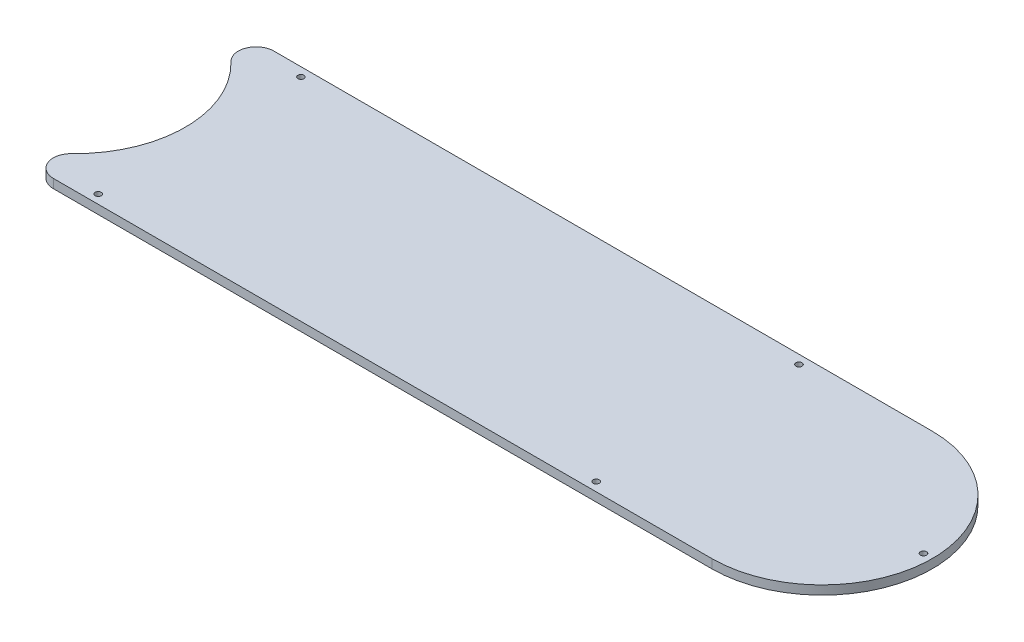
SolidWorks part; units mm, degrees
ref_plane "Front Plane" through (0, 0, 0) normal (0, 0, 1) x (1, 0, 0)
ref_plane "Top Plane" through (0, 0, 0) normal (0, 1, 0) x (1, 0, 0)
ref_plane "Right Plane" through (0, 0, 0) normal (1, 0, 0) x (0, 0, -1)
sketch "Sketch1" plane through (0, 0, 0) normal (0, 1, 0) x (1, 0, 0)
  line L0 (0, 0) -> (266.7, 0) construction
  line L1 (266.7, 39.37) -> (0, 39.37)
  line L2 (0, -39.37) -> (266.7, -39.37)
  arc A0 (0, -39.37) -> (0, 39.37) centre (0, 0) ccw
  arc A1 (266.7, -39.37) -> (266.7, 39.37) centre (266.7, 0) ccw
  circle A2 centre (302.895, 0) radius 1.0922
  circle A3 centre (222.25, 36.195) radius 1.0922
  circle A4 centre (44.45, 36.195) radius 1.0922
  circle A5 centre (44.45, -36.195) radius 1.0922
  circle A6 centre (222.25, -36.195) radius 1.0922
  dimension "D1" = 78.74
  dimension "D3" = 2.1844
  dimension "D2" = 266.7
  dimension "D4" = 3.175
  dimension "D5" = 3.175
  dimension "D6" = 44.45
  dimension "D7" = 44.45
extrude "Boss-Extrude1" add sketch "Sketch1" along normal blind 3.175
fillet "Fillet1" radius 6.35 2 edges at (0, 1.5875, 39.37) (0, 1.5875, -39.37)
